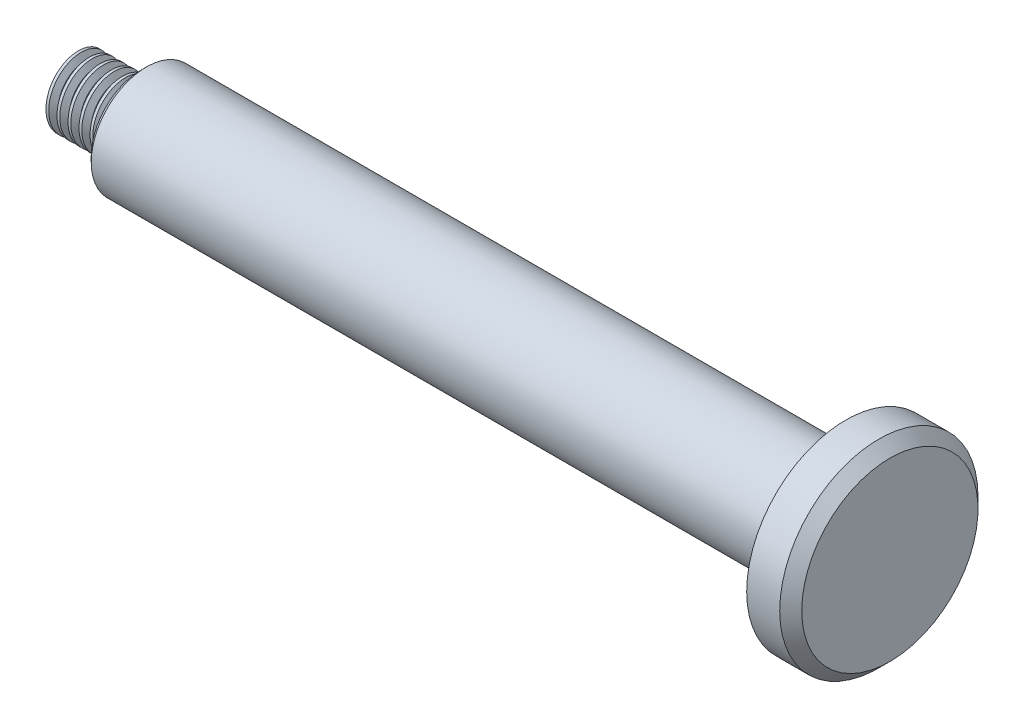
SolidWorks part; units mm, degrees
ref_plane "Front Plane" through (0, 0, 0) normal (0, 0, 1) x (1, 0, 0)
ref_plane "Top Plane" through (0, 0, 0) normal (0, 1, 0) x (1, 0, 0)
ref_plane "Right Plane" through (0, 0, 0) normal (1, 0, 0) x (0, 0, -1)
sketch "Sketch2" plane through (0, 0, 0) normal (0, 0, 1) x (1, 0, 0)
  line L0 (0, 0) -> (74, 0)
  line L1 (74, 0) -> (74, 8)
  line L2 (73, 9) -> (70, 9)
  line L3 (70, 9) -> (70, 5)
  line L4 (70, 5) -> (6.5, 5)
  line L5 (6, 4.5) -> (6, 2.5)
  line L6 (6, 2.5) -> (0, 2.5)
  line L7 (0, 2.5) -> (0, 0)
  line L8 (6.5, 5) -> (6, 4.5)
  line L9 (74, 8) -> (73, 9)
  point P4 (74, 9)
  point P7 (6, 5)
  dimension "D1" = 2.5
  dimension "D2" = 64
  dimension "D3" = 74
  dimension "D4" = 4
  dimension "D5" = 9
  dimension "D6" = 5
revolve "Revolve1" add sketch "Sketch2" angle 360 about L0
fillet "Fillet1" radius 0.5 1 edges at (70, 0, 5)
thread "Thread1" pitch 1 method extrude profile "Thread Profile1" start angle 0, offset 1, length 0, pitch 1, diameter 5
ref_plane "Plane1" through (7, 0, 2.5) normal (0, 1, 0) x (0, 0, -1)
sketch "Thread Profile1" plane through (7, 0, 2.5) normal (0, 1, 0) x (0, 0, -1)
  line L0 (0, 0) -> (0, 1) construction
  line L11 (0, 0) -> (0, 0.875)
  line L12 (0, 0.875) -> (-0.5413, 0.5625)
  line L13 (-0.5413, 0.5625) -> (-0.5413, 0.3125)
  line L15 (-0.5413, 0.3125) -> (0, 0)
  line L17 (-0.5413, 0.4375) -> (0, 0.4375) construction
  point P2 (0, 0)
  dimension "Pitch" = 1
  dimension "Profile_Angle" = 60
  dimension "Profile_Land" = 0.25
  dimension "Profile_Height" = 0.5413
other "SurfaceCut1"
